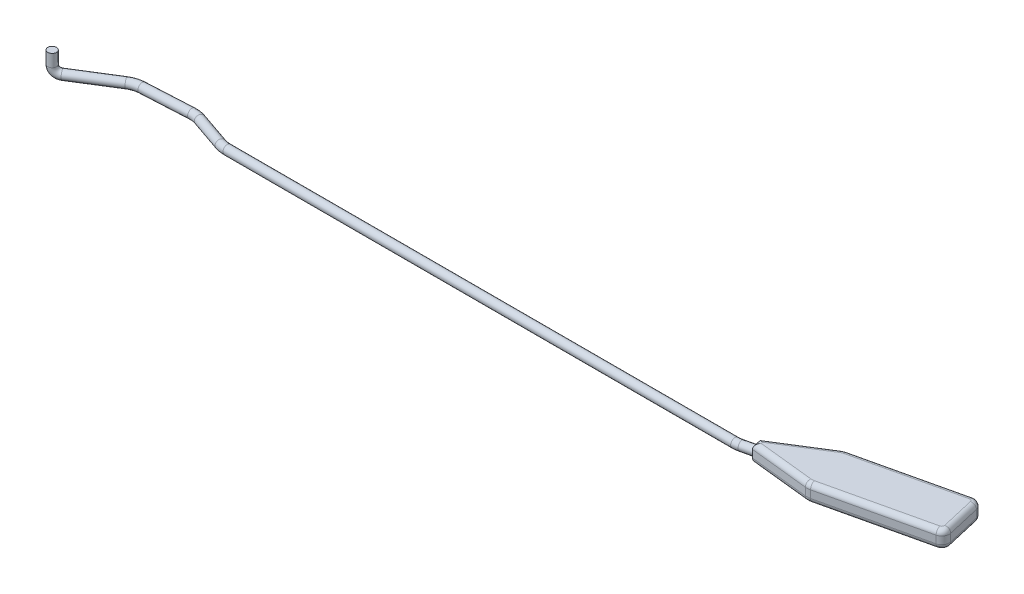
SolidWorks part; units mm, degrees
ref_plane "Front Plane" through (0, 0, 0) normal (0, 0, 1) x (1, 0, 0)
ref_plane "Top Plane" through (0, 0, 0) normal (0, 1, 0) x (1, 0, 0)
ref_plane "Right Plane" through (0, 0, 0) normal (1, 0, 0) x (0, 0, -1)
sketch "Sketch1" plane through (0, 0, 0) normal (0, 1, 0) x (1, 0, 0)
  line L4 (0, 0) -> (-4.7361, -1.0934)
  line L5 (-6.9856, -1.3497) -> (-210.6728, -1.3497)
  line L6 (-213.9285, -0.8049) -> (-226.5821, 3.5521)
  line L7 (-230.3612, 4.0832) -> (-249.3052, 3.0904)
  line L8 (-254.081, 1.5846) -> (-268.8488, -7.6433)
  arc A3 (-254.081, 1.5846) -> (-249.3052, 3.0904) centre (-248.7818, -6.8959) cw
  arc A4 (-230.3612, 4.0832) -> (-226.5821, 3.5521) centre (-229.8378, -5.9031) cw
  arc A5 (-213.9285, -0.8049) -> (-210.6728, -1.3497) centre (-210.6728, 8.6503) ccw
  arc A6 (-6.9856, -1.3497) -> (-4.7361, -1.0934) centre (-6.9856, 8.6503) ccw
  point P1 (-272.4106, -9.869)
  point P13 (-251.8878, 2.9551)
  point P18 (-228.42, 4.185)
  point P21 (-212.3462, -1.3497)
  point P24 (-5.8462, -1.3497)
  dimension "D7" = 161
  dimension "D8" = 158
  dimension "D9" = 151
  dimension "D11" = 10
  dimension "D1" = 6
  dimension "D2" = 167
  dimension "D3" = 206.5
  dimension "D4" = 17
  dimension "D5" = 23.5
  dimension "D6" = 20
  dimension "D10" = 24.2
sketch3d "3DSketch2"
  line L0 (-272.4106, 3, 9.869) -> (-272.4106, 8, 9.869)
  line L1 (-269.8664, 0, 8.2792) -> (-268.8488, 0, 7.6433)
  arc A0 (-269.8664, 0, 8.2792) -> (-272.4106, 3, 9.869) centre (-269.8664, 3, 8.2792) ccw
  point P0 (-272.4106, 0, 9.869)
  point P9 (-272.4106, 0, 9.869)
  point P10 (-271.4562, 3, 5.7351)
  dimension "D2" = 3
  dimension "D1" = 8
ref_plane "Plane3" through (0, 0, 0) normal (-0.9744, 0, 0.225) x (0.225, 0, 0.9744)
sketch "Sketch11" plane through (0, 0, 0) normal (-0.9744, 0, 0.225) x (0.225, 0, 0.9744)
  circle A0 centre (0, 0) radius 1.75
  dimension "D1" = 3.5
sweep "Sweep1" add profiles "Sketch11" path "Sketch1"
sketch "Sketch3" plane through (0, 0, 0) normal (0, 1, 0) x (1, 0, 0)
  line L0 (0, 0) -> (-4.7361, -1.0934) construction
  line L2 (8.1234, 8.2898) -> (40.7356, 15.8189)
  line L3 (43.5474, 3.6393) -> (10.9352, -3.8898)
  line L4 (7.971, -3.8223) -> (0.3937, -1.7051)
  line L5 (0, 0) -> (32.6224, 7.5315) construction
  line L6 (5.4887, 6.9297) -> (-0.3937, 1.7051)
  line L7 (-0.6014, 2.6048) -> (0.6014, -2.6048) construction
  line L8 (-0.3937, 1.7051) -> (-5.1297, 0.6117) construction
  line L9 (-4.3424, -2.7986) -> (0.3937, -1.7051) construction
  arc A0 (43.5474, 3.6393) -> (40.7356, 15.8189) centre (42.1415, 9.7291) ccw
  arc A1 (8.1234, 8.2898) -> (5.4887, 6.9297) centre (9.4731, 2.4436) ccw
  arc A2 (10.9352, -3.8898) -> (7.971, -3.8223) centre (9.5855, 1.9564) cw
  point P11 (6.6326, 7.9457)
  point P18 (9.4445, -4.234)
  dimension "D2" = 35
  dimension "D4" = 6
  dimension "D6" = 6.25
  dimension "D7" = 6
  dimension "D11" = 43.25
  dimension "D3" = 12.5
  dimension "D5" = 35
sketch "Sketch8" plane through (-196.7871, 0, 122.9662) normal (-0.848, 0, 0.5299) x (0.5299, 0, 0.848)
  circle A0 centre (-135.9862, 0) radius 1.75
  dimension "D1" = 3.5
sweep "Sweep3" add profiles "Sketch8" path "3DSketch2"
ref_plane "Plane1" through (-0.3937, 0, -1.7051) normal (0.7477, 0, -0.6641) x (-0.6641, 0, -0.7477)
sketch "Sketch5" plane through (0, 0, 0) normal (0, 1, 0) x (1, 0, 0)
  line L0 (-0.3937, 1.7051) -> (19.8139, 14.3709)
  line L1 (21.6507, 15.1332) -> (62.5742, 24.5811)
  line L2 (67.017, 5.3373) -> (26.0935, -4.1106)
  line L3 (24.1084, -4.2306) -> (0.3937, -1.7051)
  line L4 (-0.6014, 2.6048) -> (0.6014, -2.6048) construction
  line L6 (69.2653, 8.9353) -> (66.1722, 22.3329)
  line L8 (0, 0) -> (32.6224, 7.5315) construction
  line L14 (-0.3937, 1.7051) -> (0.3937, -1.7051)
  arc A0 (67.017, 5.3373) -> (69.2653, 8.9353) centre (66.3421, 8.2605) ccw
  arc A1 (19.8139, 14.3709) -> (21.6507, 15.1332) centre (23.0004, 9.287) cw
  arc A2 (24.1084, -4.2306) -> (26.0935, -4.1106) centre (24.7438, 1.7356) ccw
  arc A3 (62.5742, 24.5811) -> (66.1722, 22.3329) centre (63.2491, 21.658) cw
  dimension "D2" = 6
  dimension "D3" = 6
  dimension "D6" = 3
  dimension "D1" = 19.75
  dimension "D4" = 69.5
  dimension "D5" = 45
  dimension "D7" = 9.875
  dimension "D8" = 45
extrude "Boss-Extrude1" add sketch "Sketch5" along normal mid plane 7
sketch "Sketch10" plane through (0, 8, 0) normal (0, 1, 0) x (-1, 0, 0)
  circle A0 centre (272.4106, 9.869) radius 1.75 construction
  point P0 (270.6727, 9.6635)
fillet "Fillet1" radius 2 10 edges at (42.1124, 3.5, -19.8572) (64.8388, 3.5, -24.2022) (67.7187, 3.5, -15.6341) (68.8863, 3.5, -6.6707) (46.5552, 3.5, -0.6134) (25.1059, 3.5, 4.2534) (12.251, 3.5, 2.9679) (0, 3.5, 0) (9.7101, 3.5, -8.038) (20.7005, 3.5, -14.8287)
fillet "Fillet2" radius 2 10 edges at (9.7101, -3.5, -8.038) (0, -3.5, 0) (12.251, -3.5, 2.9679) (25.1059, -3.5, 4.2534) (46.5552, -3.5, -0.6134) (68.8863, -3.5, -6.6707) (67.7187, -3.5, -15.6341) (64.8388, -3.5, -24.2022) (42.1124, -3.5, -19.8572) (20.7005, -3.5, -14.8287)
